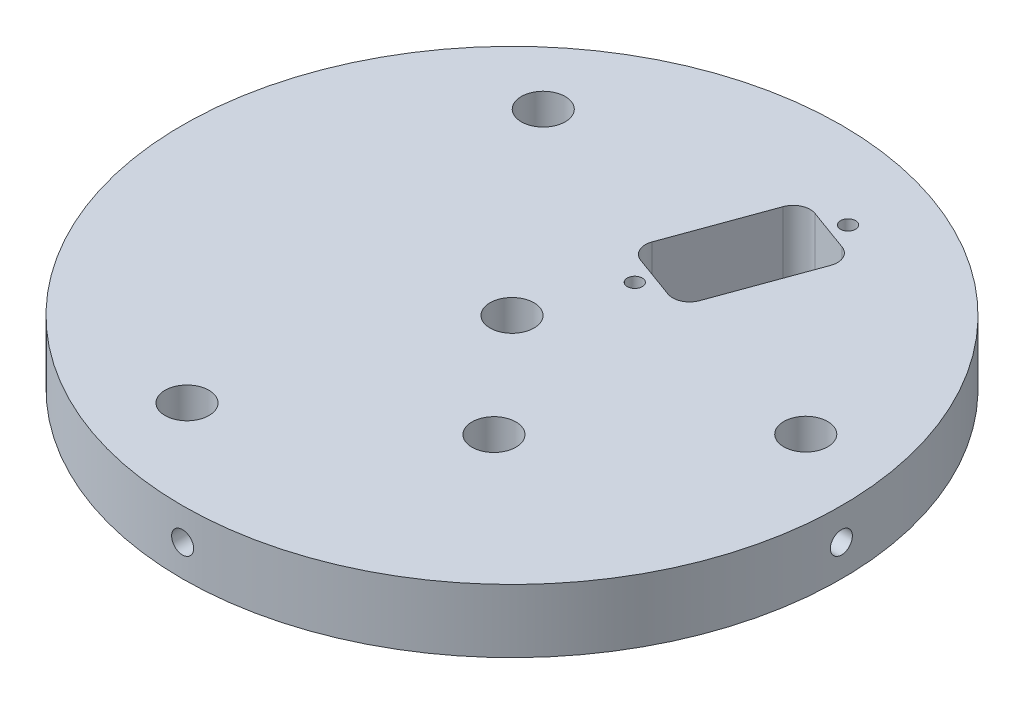
SolidWorks part; units mm, degrees
material "6061-T6 (SS)"
ref_plane "Front Plane" through (0, 0, 0) normal (0, 0, 1) x (1, 0, 0)
ref_plane "Top Plane" through (0, 0, 0) normal (0, 1, 0) x (1, 0, 0)
ref_plane "Right Plane" through (0, 0, 0) normal (1, 0, 0) x (0, 0, -1)
sketch "Sketch1" plane through (0, 0, 0) normal (0, 1, 0) x (1, 0, 0)
  line L0 (0, 0) -> (-50.3682, 60.0265)
  line L1 (0, 0) -> (50.3682, 60.0265)
  line L2 (0, 0) -> (0, 72.1431) construction
  circle A0 centre (0, 0) radius 78.359
  circle A1 centre (0, 0) radius 51.1048
  circle A2 centre (0, 0) radius 76.1746
  dimension "D1" = 156.718
  dimension "D2" = 102.2096
  dimension "D3" = 152.3492
  dimension "D4" = 80
extrude "Boss-Extrude1" add sketch "Sketch1" along normal blind 25.4 contours L2 A2 L1 A0 | L2 A1 L1 A2 | L2 A2 L1 A1 | L2 A0 L1 A2 | A2 L2 A1 L0 | A0 L2 A2 L0 | A2 L2 A0 L0 | A1 L2 A2 L0 region at (-22.4568, 0, 48.1587) region at (-40.1048, 0, -49.4238) region at (-33.0764, 0, 70.9325) region at (-48.8794, 0, -59.85)
ref_plane "Plane1" through (0, 12.7, 0) normal (0, 1, 0) x (1, 0, 0)
sketch "Sketch6" plane through (0, 25.4, 0) normal (0, 1, 0) x (1, 0, 0)
  circle A0 centre (0, 0) radius 49.5173
  dimension "D1" = 99.0346
extrude "Boss-Extrude5" add sketch "Sketch6" along normal blind 9.525
sketch "Sketch7" plane through (0, 0, 0) normal (0, -1, 0) x (1, 0, 0)
  circle A0 centre (0, 0) radius 49.5173
  dimension "D1" = 99.0346
extrude "Boss-Extrude6" add sketch "Sketch7" along normal blind 9.525
sketch "Sketch8" plane through (0, -9.525, 0) normal (0, -1, 0) x (1, 0, 0)
  circle A0 centre (0, 0) radius 46.99
  dimension "D1" = 93.98
ref_plane "Plane2" through (0, 0, -49.5173) normal (0, 0, -1) x (-1, 0, 0)
ref_plane "Plane5" through (0, 25.4, 0) normal (0, 1, 0) x (1, 0, 0)
ref_axis "Axis1" through (0, 0, 0) along (0, 1, 0)
ref_plane "Plane3" through (0, 34.925, 0) normal (0, 1, 0) x (1, 0, 0)
sketch "Sketch9" plane through (0, 34.925, 0) normal (0, 1, 0) x (1, 0, 0)
  line L0 (0, 0) -> (-26.8004, -73.6334) construction
  line L1 (0, 0) -> (32.0596, -38.2071) construction
  line L2 (0, 0) -> (0, -86.0416) construction
  circle A0 centre (0, 0) radius 3.3
  circle A1 centre (-13.031, -35.8023) radius 3.3
  circle A4 centre (14.1499, -16.8632) radius 3.3
  circle A5 centre (-24.4902, 29.1863) radius 3.3
  circle A6 centre (37.5212, 6.616) radius 3.3
  point P15 (-1.3039, -1.0954)
  point P18 (0, 0)
  dimension "D1" = 6.6
  dimension "D2" = 6.6
  dimension "D6" = 6.6
  dimension "D3" = 38.1
  dimension "D4" = 60
  dimension "D7" = 22.0133
  dimension "D8" = 20
extrude "Cut-Extrude6" cut sketch "Sketch9" against normal through all
sketch "Sketch10" plane through (0, 25.4, 0) normal (0, 1, 0) x (1, 0, 0)
  circle A0 centre (0, 0) radius 82.3228
extrude "Cut-Extrude7" cut sketch "Sketch10" against normal through all
hole_wizard "Tap Drill for #4-40 Tap1" positions "Sketch12" profile "Sketch13" hole size "#4-40" standard "ANSI Inch" end condition through all
sketch "Sketch12" plane through (0, 34.925, 0) normal (0, 1, 0) x (1, 0, 0)
  line L0 (0, 0) -> (18.0627, 49.6269) construction
  line L2 (0, 0) -> (-24.4902, 29.1863) construction
  circle A0 centre (0, 0) radius 14.3933 construction
  point P0 (4.9228, 13.5253)
  point P2 (13.4733, 37.0176)
  dimension "D3" = 28.7867
  dimension "D1" = 60
  dimension "D2" = 25
sketch "Sketch13" plane through (4.9228, 34.925, -13.5253) normal (1, 0, 0) x (0, 0, 1)
  line L0 (0, 0) -> (0, 9.525)
  line L1 (0, 9.525) -> (1.1303, 9.525)
  line L2 (1.1303, 9.525) -> (1.1303, 0)
  line L5 (1.1303, 0) -> (0, 0)
  line L11 (0, -6.35) -> (0, 107.95) construction
  dimension "Thru Hole Dia." = 2.2606
  dimension "Thru Hole Depth" = 9.525
sketch "Sketch14" plane through (0, 34.925, 0) normal (0, 1, 0) x (1, 0, 0)
  line L0 (4.9228, 13.5253) -> (13.4733, 37.0176) construction
  line L1 (12.1824, 16.0187) -> (17.4317, 30.4411)
  line L2 (8.9269, 14.5007) -> (2.4825, 16.8462)
  line L3 (15.9137, 33.6967) -> (9.4692, 36.0423)
  line L4 (0.9644, 20.1018) -> (6.2137, 34.5242)
  arc A0 (17.4317, 30.4411) -> (15.9137, 33.6967) centre (15.0449, 31.3099) ccw
  arc A1 (9.4692, 36.0423) -> (6.2137, 34.5242) centre (8.6005, 33.6555) ccw
  arc A2 (8.9269, 14.5007) -> (12.1824, 16.0187) centre (9.7956, 16.8875) ccw
  arc A3 (2.4825, 16.8462) -> (0.9644, 20.1018) centre (3.3512, 19.2331) cw
  point P0 (5.7047, 15.6734)
  dimension "D4" = 2.54
  dimension "D5" = 2.54
  dimension "D2" = 2.286
  dimension "D3" = 11.938
extrude "Cut-Extrude9" cut sketch "Sketch14" against normal through all
ref_plane "Plane6" through (49.5173, 0, 0) normal (1, 0, 0) x (0, 0, -1)
hole_wizard "Tap Drill for M4x0.7 Tap1" positions "Sketch16" profile "Sketch17" hole size "M4x0.7" standard "ANSI Metric"
sketch "Sketch16" plane through (49.5173, 0, 0) normal (1, 0, 0) x (0, 0, -1)
  line L1 (49.5173, 34.925) -> (-49.5173, 34.925) construction
  point P0 (0, 30.1625)
  dimension "D1" = 4.7625
sketch "Sketch17" plane through (49.5173, 30.1625, 0) normal (0, 1, 0) x (0, 0, -1)
  line L0 (0, 0) -> (0, 10.6434)
  line L1 (0, 10.6434) -> (1.65, 9.652)
  line L2 (1.65, 9.652) -> (1.65, 0)
  line L5 (1.65, 0) -> (0, 0)
  line L10 (0, 10.6434) -> (-1.65, 9.652) construction
  line L11 (0, -6.35) -> (0, 107.95) construction
  dimension "Hole Dia." = 3.3
  dimension "Hole Depth" = 9.652
  dimension "Drill Angle" = 118
pattern_circular "CirPattern1" count 4 over 360 about axis through (0, 34.925, 0) along (0, 1, 0) of "Tap Drill for M4x0.7 Tap1"
equation "\"AB_Coupler_OD_Length\"= 1in"
equation "\"AB_Coupling_Section_Length\"= 0.375in"
equation "\"AB_Coupler_Length\"= \"AB_Coupler_OD_Length\" + \"AB_Coupling_Section_Length\" * 2"
equation "\"Cutout_Angle\" = 60"
equation "\"AB_Coupler_Num_Screws\"= 4"
equation "\"Num_Cutouts\" = 4"
equation "\"AB_Coupler_OD\"= 4.024in"
equation "\"AB_Coupler_ID\"= 3.7in"
equation "\"AB_Coupler_Surface_Diameter\"= 3.899in"
equation "\"D2@Sketch1\"= \"Body_Tube_OD\""
equation "\"AB_Coupling_Screw_Diameter\"= 0.1065in"
equation "\"Aft_Section_Length\" = 32in"
equation "\"Mid_Coupler_Length\" = 12in"
equation "\"Lead_Screw_Dist\" = 2in"
equation "\"Lead_Screw_Diam\" = 0.375in"
equation "\"Lead_Screw_Length\" = \"Mid_Coupler_Length\" + 2*0.375in + 2*0.5in"
equation "\"Paddle_Pin_Offset\" = 0.25in"
equation "\"Paddle_Pin_Radius\" = 2.25*2/3in"
equation "\"D1@Sketch6\"=\"AB_Coupler_Surface_Diameter\""
equation "\"D1@Boss-Extrude5\"=\"AB_Coupling_Section_Length\""
equation "\"D1@Sketch7\"=\"AB_Coupler_Surface_Diameter\""
equation "\"D1@Boss-Extrude6\"=\"AB_Coupling_Section_Length\""
equation "\"D1@Sketch8\"=\"AB_Coupler_ID\""
equation "\"D3@Sketch9\"=\"Paddle_Pin_Radius\""
equation "\"Motor_OD\" = 54.4mm"
equation "\"AB_Paddle_Height\" = 0.375in"
equation "\"AB_Central_Bushing_Length\" = 0.75in"
equation "\"Paddle_Gear_OD\" = 3.2in"
equation "\"Fwd_BKHD_From_Top\" = 18in"
equation "\"Fin_Thickness\" = 0.118in"
equation "\"DB9_Hole_Dist\" = 25mm"
equation "\"D2@Sketch12\"=\"DB9_Hole_Dist\""
equation "\"Drive_Gear_OD\" = 1.7*2/3in"
equation "\"D3@Sketch12\"=\"Drive_Gear_OD\""
equation "\"DB9_Relief_Width\" = 0.47in"
equation "\"D3@Sketch14\"=\"DB9_Relief_Width\""
equation "\"DB9_Relief_Hole_Offset\" = 0.09in"
equation "\"D2@Sketch14\"=\"DB9_Relief_Hole_Offset\""
equation "\"D1@Sketch14\"=\"DB9_Relief_Hole_Offset\""
equation "\"Airbrakes_Wire_Hole_Dia\" = 0.25in"
equation "\"Airbrakes_Wire_Hole_Dist\" = 1.1*2/3in"
equation "\"Servo_Gear_Offset\" = 0.5in"
equation "\"Motor_Length\" = 401mm"
equation "\"Body_Tube_OD\"= 4.024in"
equation "\"Body_Tube_ID\"= 3.90in"
equation "\"Coupler_OD\" = 3.899in"
equation "\"Coupler_ID\" = 3.755in"
equation "\"Fwd_Section_Length\" = 20in"
equation "\"Mid_Section_Length\" = 4in"
equation "\"Aft_Upper_Tube_Length\" = 10in"
equation "\"Aft_Lower_Tube_Length\" = 18in"
equation "\"Nosecone_Coupler_Length\" = 5in"
equation "\"Avionics_Bulkhead_Thickness\" = 0.25in"
equation "\"Avionics_Bulkhead_Lip\" = 0.125in"
equation "\"Avionics_Board_Length\" = \"Mid_Coupler_Length\" - 2*\"Avionics_Bulkhead_Lip\""
equation "\"Lead_Screw_Hole_Diam\" = 0.386in"
equation "\"Centering_Ring_Cutout_Dia\"=1.5in"
equation "\"D7@Sketch9\"=\"Drive_Gear_OD\"/2+.3"
equation "\"D1@Sketch16\"=.375/2"
